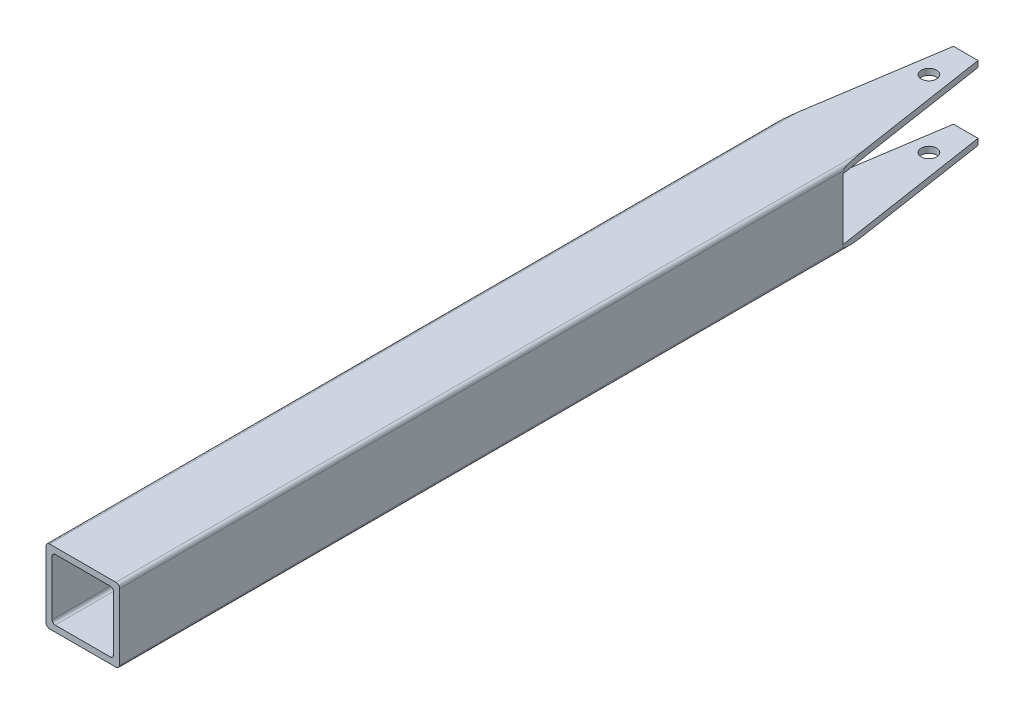
SolidWorks part; units mm, degrees
ref_plane "Front" through (0, 0, 0) normal (0, 0, 1) x (1, 0, 0)
ref_plane "Top" through (0, 0, 0) normal (0, 1, 0) x (1, 0, 0)
ref_plane "Right" through (0, 0, 0) normal (1, 0, 0) x (0, 0, -1)
sketch "Sketch1" plane through (0, 0, 0) normal (0, 0, 1) x (1, 0, 0)
  line L0 (-31.75, 0) -> (-38.1, 0) construction
  line L1 (34.29, -38.1) -> (-34.29, -38.1)
  line L2 (38.1, -34.29) -> (38.1, 34.29)
  line L3 (34.29, 38.1) -> (-34.29, 38.1)
  line L4 (-38.1, -34.29) -> (-38.1, 34.29)
  line L5 (38.1, -38.1) -> (-38.1, 38.1) construction
  line L6 (38.1, 38.1) -> (-38.1, -38.1) construction
  line L7 (28.575, 31.75) -> (-28.575, 31.75)
  line L8 (31.75, 28.575) -> (31.75, -28.575)
  line L9 (28.575, -31.75) -> (-28.575, -31.75)
  line L10 (-31.75, 28.575) -> (-31.75, -28.575)
  line L11 (31.75, 31.75) -> (-31.75, -31.75) construction
  line L12 (31.75, -31.75) -> (-31.75, 31.75) construction
  line L13 (0, -31.75) -> (0, -38.1) construction
  line L14 (31.75, -28.575) -> (31.75, -38.1) construction
  line L16 (31.75, -38.1) -> (38.1, -38.1) construction
  arc A0 (-28.575, -31.75) -> (-31.75, -28.575) centre (-28.575, -28.575) cw
  arc A1 (31.75, -28.575) -> (28.575, -31.75) centre (28.575, -28.575) cw
  arc A2 (28.575, 31.75) -> (31.75, 28.575) centre (28.575, 28.575) cw
  arc A3 (-28.575, 31.75) -> (-31.75, 28.575) centre (-28.575, 28.575) ccw
  arc A4 (34.29, -38.1) -> (38.1, -34.29) centre (34.29, -34.29) ccw
  arc A5 (38.1, 34.29) -> (34.29, 38.1) centre (34.29, 34.29) ccw
  arc A6 (-34.29, 38.1) -> (-38.1, 34.29) centre (-34.29, 34.29) ccw
  arc A7 (-34.29, -38.1) -> (-38.1, -34.29) centre (-34.29, -34.29) cw
  point P0 (0, 0)
  point P6 (0, 0)
  dimension "D2" = 3.175
  dimension "D3" = 3.81
sketch "Sketch2" plane through (0, 0, 0) normal (1, 0, 0) x (0, 0, -1)
  line L0 (-457.2, 0) -> (457.2, 0) construction
  dimension "Length" = 914.4
ref_plane "Plane1" through (38.1, 0, 0) normal (1, 0, 0) x (0, 0, -1)
sketch "Sketch5" plane through (38.1, 0, 0) normal (1, 0, 0) x (0, 0, -1)
  line L0 (-457.2, 38.1) -> (-457.2, -38.1) construction
  line L1 (457.2, 38.1) -> (457.2, -38.1) construction
sketch "Sketch4" plane through (0, 0, 0) normal (0, 0, 1) x (1, 0, 0)
  line L0 (38.1, -34.29) -> (38.1, 34.29) construction
  line L1 (34.29, 38.1) -> (-34.29, 38.1) construction
  line L2 (-38.1, -34.29) -> (-38.1, 34.29) construction
  line L3 (34.29, -38.1) -> (-34.29, -38.1) construction
  line L4 (31.75, 28.575) -> (31.75, -28.575) construction
  line L5 (28.575, -31.75) -> (-28.575, -31.75) construction
  line L6 (-31.75, 28.575) -> (-31.75, -28.575) construction
  line L7 (28.575, 31.75) -> (-28.575, 31.75) construction
  line L8 (38.1, -34.29) -> (38.1, 34.29)
  line L9 (34.29, 38.1) -> (-34.29, 38.1)
  line L10 (-38.1, -34.29) -> (-38.1, 34.29)
  line L11 (34.29, -38.1) -> (-34.29, -38.1)
  line L12 (31.75, 28.575) -> (31.75, -28.575)
  line L13 (28.575, -31.75) -> (-28.575, -31.75)
  line L14 (-31.75, 28.575) -> (-31.75, -28.575)
  line L15 (28.575, 31.75) -> (-28.575, 31.75)
  arc A0 (38.1, 34.29) -> (34.29, 38.1) centre (34.29, 34.29) ccw construction
  arc A1 (-34.29, 38.1) -> (-38.1, 34.29) centre (-34.29, 34.29) ccw construction
  arc A2 (-38.1, -34.29) -> (-34.29, -38.1) centre (-34.29, -34.29) ccw construction
  arc A3 (34.29, -38.1) -> (38.1, -34.29) centre (34.29, -34.29) ccw construction
  arc A4 (28.575, -31.75) -> (31.75, -28.575) centre (28.575, -28.575) ccw construction
  arc A5 (-31.75, -28.575) -> (-28.575, -31.75) centre (-28.575, -28.575) ccw construction
  arc A6 (-28.575, 31.75) -> (-31.75, 28.575) centre (-28.575, 28.575) ccw construction
  arc A7 (31.75, 28.575) -> (28.575, 31.75) centre (28.575, 28.575) ccw construction
  arc A8 (38.1, 34.29) -> (34.29, 38.1) centre (34.29, 34.29) ccw
  arc A9 (-34.29, 38.1) -> (-38.1, 34.29) centre (-34.29, 34.29) ccw
  arc A10 (-38.1, -34.29) -> (-34.29, -38.1) centre (-34.29, -34.29) ccw
  arc A11 (34.29, -38.1) -> (38.1, -34.29) centre (34.29, -34.29) ccw
  arc A12 (28.575, -31.75) -> (31.75, -28.575) centre (28.575, -28.575) ccw
  arc A13 (-31.75, -28.575) -> (-28.575, -31.75) centre (-28.575, -28.575) ccw
  arc A14 (-28.575, 31.75) -> (-31.75, 28.575) centre (-28.575, 28.575) ccw
  arc A15 (31.75, 28.575) -> (28.575, 31.75) centre (28.575, 28.575) ccw
extrude "Boss-Extrude1" add sketch "Sketch4" along normal up to vertex (457.2 mm away) and the other way up to vertex (457.2 mm away) up to point (0, 0, 457.2) other way up to point (0, 0, -457.2)
sketch "Sketch6" plane through (-38.1, 0, 0) normal (-1, 0, 0) x (0, 0, 1)
  line L0 (-457.2, -31.75) -> (-371.4675, -31.75) construction
  line L1 (-457.2, 31.75) -> (-292.1, 31.75)
  line L2 (-457.2, 31.75) -> (-457.2, -31.75)
  line L3 (-457.2, -31.75) -> (-292.1, -31.75)
  line L4 (-292.1, 31.75) -> (-292.1, -31.75)
  point P5 (-457.2, -31.75)
  dimension "D1" = 165.1
extrude "side cut" cut sketch "Sketch6" against normal through all
sketch "Sketch7" plane through (0, -38.1, 0) normal (0, -1, 0) x (1, 0, 0)
  line L0 (0, -457.2) -> (0, -341.7828) construction
  line L1 (-34.29, -457.2) -> (34.29, -457.2) construction
  line L2 (-38.1, -292.1) -> (-38.1, -457.2)
  line L3 (-38.1, -457.2) -> (-12.7, -457.2)
  line L4 (-12.7, -457.2) -> (-38.1, -292.1)
  line L5 (12.7, -457.2) -> (38.1, -292.1)
  line L6 (38.1, -457.2) -> (12.7, -457.2)
  line L7 (38.1, -292.1) -> (38.1, -457.2)
  dimension "D1" = 25.4
extrude "triangle cut" cut sketch "Sketch7" against normal through all
sketch "Sketch8" plane through (0, 38.1, 0) normal (0, 1, 0) x (1, 0, 0)
  line L0 (0, 457.2) -> (0, 353.4841) construction
  line L1 (12.7, 457.2) -> (-12.7, 457.2) construction
  circle A0 centre (0, 419.1) radius 7.9375
  dimension "D1" = 15.875
  dimension "D2" = 38.1
extrude "Cut-Extrude4" cut sketch "Sketch8" against normal through all
sketch "Sketch9" plane through (38.1, 0, 0) normal (1, 0, 0) x (0, 0, -1)
  line L0 (411.1625, 34.925) -> (427.0375, 34.925) construction
  line L1 (411.1625, 38.1) -> (411.1625, 31.75) construction
  line L2 (427.0375, 31.75) -> (427.0375, 38.1) construction
  line L3 (411.1625, -34.925) -> (427.0375, -34.925) construction
  line L4 (411.1625, -31.75) -> (411.1625, -38.1) construction
  line L5 (427.0375, -38.1) -> (427.0375, -31.75) construction
  line L6 (419.1, -34.925) -> (419.1, 34.925) construction
  line L7 (419.1, 0) -> (-304.8, 0)
  point P18 (-304.8, 0)
  dimension "D1" = 723.9
equation "\"D3@Sketch1\"=\"Outside Width@Sketch1\"*.05"
equation "\"D2@Sketch1\"=\"D1@Sketch1\"*.05"
equation "\"mountingPointDistance\"=28.5"
equation "\"D1@Sketch9\"=\"mountingPointDistance\""
